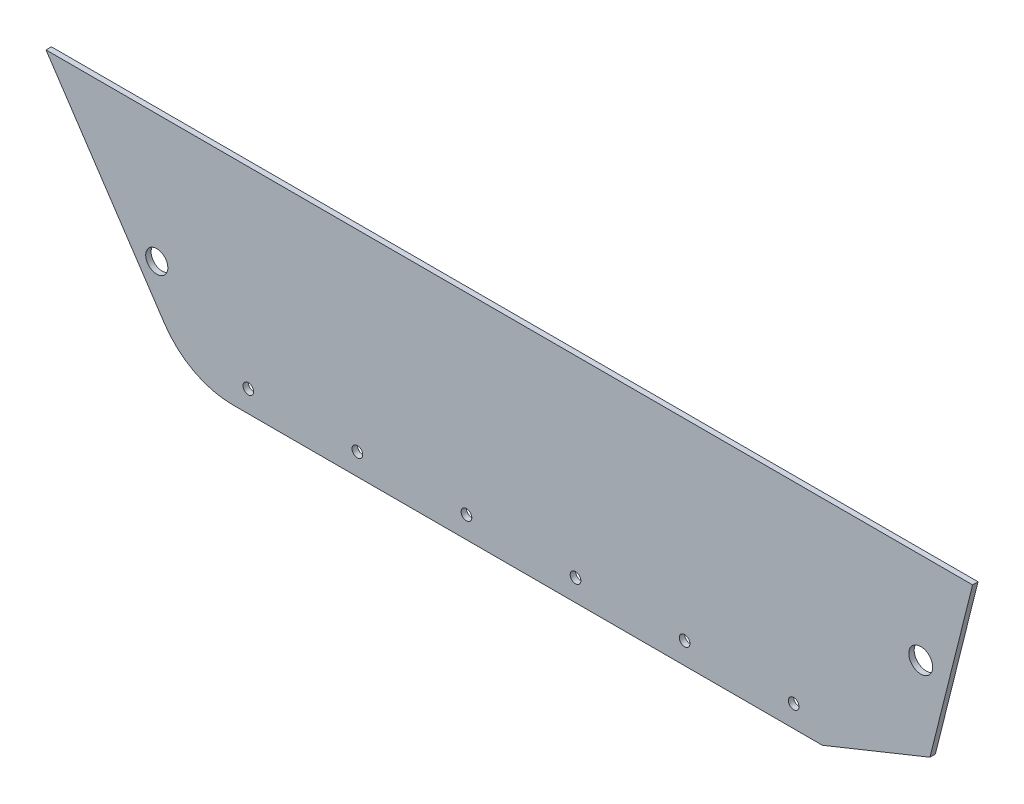
SolidWorks part; units mm, degrees
material "5052-H34"
ref_plane "Front Plane" through (0, 0, 0) normal (0, 0, 1) x (1, 0, 0)
ref_plane "Top Plane" through (0, 0, 0) normal (0, 1, 0) x (1, 0, 0)
ref_plane "Right Plane" through (0, 0, 0) normal (1, 0, 0) x (0, 0, -1)
sketch "Sketch1" plane through (0, 0, 0) normal (0, 0, 1) x (1, 0, 0)
  line L6 (-98.8794, 3.851) -> (-31.8794, -96.649)
  line L7 (428.1206, 28.9396) -> (403.1206, -71.149)
  line L9 (403.1206, -71.149) -> (366, -96.649)
  line L10 (-31.8794, -96.649) -> (366, -96.649)
  line L12 (-98.8794, 3.851) -> (-115.6052, 28.9396)
  line L13 (-115.6052, 28.9396) -> (428.1206, 28.9396)
  circle A0 centre (3.1206, -83.899) radius 3.125
  circle A1 centre (67.1206, -83.899) radius 3.125
  circle A2 centre (131.1206, -83.899) radius 3.125
  circle A3 centre (195.1206, -83.899) radius 3.125
  circle A4 centre (259.1206, -83.899) radius 3.125
  circle A5 centre (323.1206, -83.899) radius 3.125
  point P0 (-48.8794, -71.149)
  point P2 (-31.8794, -96.649)
  point P8 (48, -83.899)
  point P9 (403.1206, -71.149)
  dimension "D2" = 64
  dimension "D4" = 64
  dimension "D14" = 6.25
  dimension "D1" = 25.5
  dimension "D3" = 75
  dimension "D5" = 25
  dimension "D6" = 80
  dimension "D7" = 527
  dimension "D8" = 180
  dimension "D9" = 64
  dimension "D10" = 64
  dimension "D11" = 64
  dimension "D12" = 123.69
  dimension "D13" = 12.75
  dimension "D15" = 366
  dimension "D16" = 115.6052
extrude "Boss-Extrude1" add sketch "Sketch1" along normal blind 3.175 contours L12 L13 L7 L9 L10 L6
extrude "Cut-Extrude1" cut sketch "Sketch1<4>" along normal through all contours A0 | A1 | A2 | A3 | A4 | A5 region at (3.1206, -83.899, 0)
sketch "Sketch1<4>" plane through (0, 0, 0) normal (0, 0, 1) x (1, 0, 0) same geometry as "Sketch1"
sketch "Sketch5" plane through (0, 0, 0) normal (0, 0, -1) x (-1, 0, 0)
  line L0 (48.8794, -71.149) -> (-14.2353, -96.649)
  line L1 (31.8794, -96.649) -> (-366, -96.649) construction
  line L2 (-14.2353, -96.649) -> (31.8794, -96.649)
  line L3 (31.8794, -96.649) -> (48.8794, -71.149)
  line L6 (-366, -96.649) -> (-403.1206, -71.149)
  line L7 (-403.1206, -71.149) -> (-352, -71.149)
  line L9 (-352, -71.149) -> (-326.5, -96.649)
  line L11 (-366, -96.649) -> (-326.5, -96.649)
  dimension "D1" = 22
  dimension "D2" = 45
extrude "Cut-Extrude2" [suppressed] cut sketch "Sketch5" against normal up to next
sketch "Sketch6" plane through (0, 0, 3.175) normal (0, 0, 1) x (1, 0, 0)
  line L0 (-48.8794, -71.149) -> (14.2353, -96.649)
  line L1 (-31.8794, -96.649) -> (366, -96.649) construction
  line L2 (14.2353, -96.649) -> (-31.8794, -96.649)
  line L3 (-31.8794, -96.649) -> (-48.8794, -71.149)
  dimension "D1" = 158
fillet "Fillet1" radius 48 1 edges at (-31.8794, -96.649, 1.5875)
sketch "Sketch7" plane through (0, 0, 3.175) normal (0, 0, 1) x (1, 0, 0)
  line L0 (403.1206, -71.149) -> (340.0059, -96.649)
  line L1 (-31.8794, -96.649) -> (366, -96.649) construction
  line L2 (340.0059, -96.649) -> (366, -96.649)
  line L3 (366, -96.649) -> (403.1206, -71.149)
  dimension "D1" = 22
extrude "Cut-Extrude3" cut sketch "Sketch7" against normal blind 10
sketch "Sketch9" plane through (0, 0, 0) normal (0, 0, -1) x (-1, 0, 0)
  line L0 (-403.1206, -71.149) -> (48.8794, -71.149)
  line L1 (48.8794, -71.149) -> (48.8794, -114.9143)
  line L2 (48.8794, -114.9143) -> (-403.1206, -114.9143)
  line L3 (-403.1206, -114.9143) -> (-403.1206, -71.149)
sketch "Sketch11" plane through (0, 0, 0) normal (0, 0, -1) x (-1, 0, 0)
  circle A0 centre (-397.6786, -24.6104) radius 7
  dimension "D1" = 14
extrude "Cut-Extrude5" cut sketch "Sketch11" against normal up to next
sketch "Sketch13" plane through (0, 0, 0) normal (0, 0, -1) x (-1, 0, 0)
  line L0 (115.6052, 28.9396) -> (-428.1206, 28.9396) construction
  circle A0 centre (50.6052, -46.0604) radius 6.5
  dimension "D1" = 13
  dimension "D2" = 65
  dimension "D3" = 75
extrude "Cut-Extrude6" cut sketch "Sketch13" against normal blind 10
